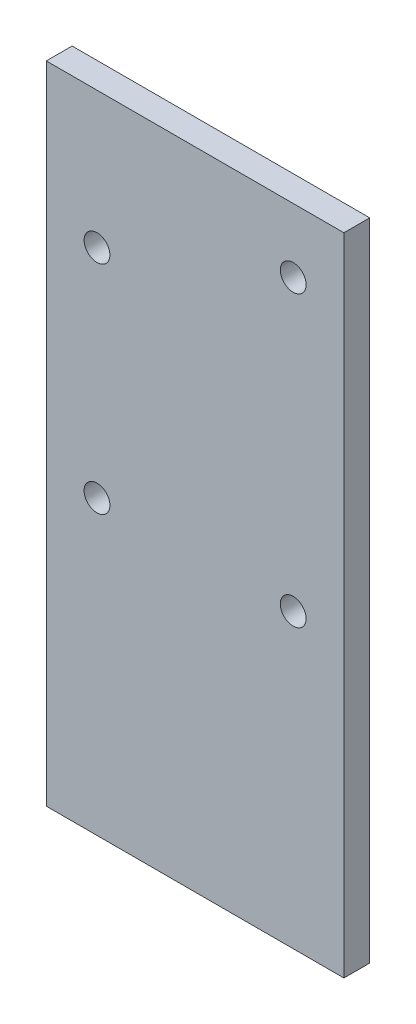
SolidWorks part; units mm, degrees
ref_plane "정면" through (0, 0, 0) normal (0, 0, 1) x (1, 0, 0)
ref_plane "윗면" through (0, 0, 0) normal (0, 1, 0) x (1, 0, 0)
ref_plane "우측면" through (0, 0, 0) normal (1, 0, 0) x (0, 0, -1)
sketch "스케치1" plane through (0, 0, 0) normal (0, 0, 1) x (1, 0, 0)
  line L1 (-28.82, 62.5) -> (28.82, 62.5)
  line L2 (-28.82, 62.5) -> (-28.82, -62.5)
  line L3 (-28.82, -62.5) -> (28.82, -62.5)
  line L4 (28.82, 62.5) -> (28.82, -62.5)
  line L5 (-28.82, 62.5) -> (28.82, -62.5) construction
  line L6 (-28.82, -62.5) -> (28.82, 62.5) construction
  point P0 (0, 0)
  dimension "D1" = 57.64
  dimension "D2" = 125
extrude "보스-돌출1" add sketch "스케치1" along normal blind 5
sketch "스케치2" plane through (0, 0, 5) normal (0, 0, 1) x (1, 0, 0)
  line L0 (28.82, 62.5) -> (-28.82, 62.5) construction
  line L1 (28.82, -62.5) -> (28.82, 62.5) construction
  circle A10 centre (-19, 36.1) radius 5.8
  circle A11 centre (-19, 36.1) radius 2.5
  circle A12 centre (19, 50.1) radius 5.8
  circle A13 centre (19, 50.1) radius 2.5
  circle A14 centre (-19, -5.9) radius 5.8
  circle A15 centre (-19, -5.9) radius 2.5
  circle A16 centre (19, -5.9) radius 5.8
  circle A17 centre (19, -5.9) radius 2.5
  dimension "D3" = 5
  dimension "D4" = 11.6
  dimension "D5" = 5
  dimension "D8" = 11.6
  dimension "D9" = 11.6
  dimension "D10" = 42
  dimension "D11" = 56
  dimension "D12" = 38
  dimension "D13" = 9.82
  dimension "D2" = 11.6
  dimension "D6" = 5
  dimension "D7" = 5
  dimension "D14" = 12.4
  dimension "D15" = 38
  dimension "D16" = 68.4
  dimension "D17" = 38
extrude "컷-돌출1" cut sketch "스케치2" against normal blind 5 contours A13 | A17 | A15 | A11 region at (19, 50.1, 5) region at (-19, -5.9, 5) region at (19, -5.9, 5)
